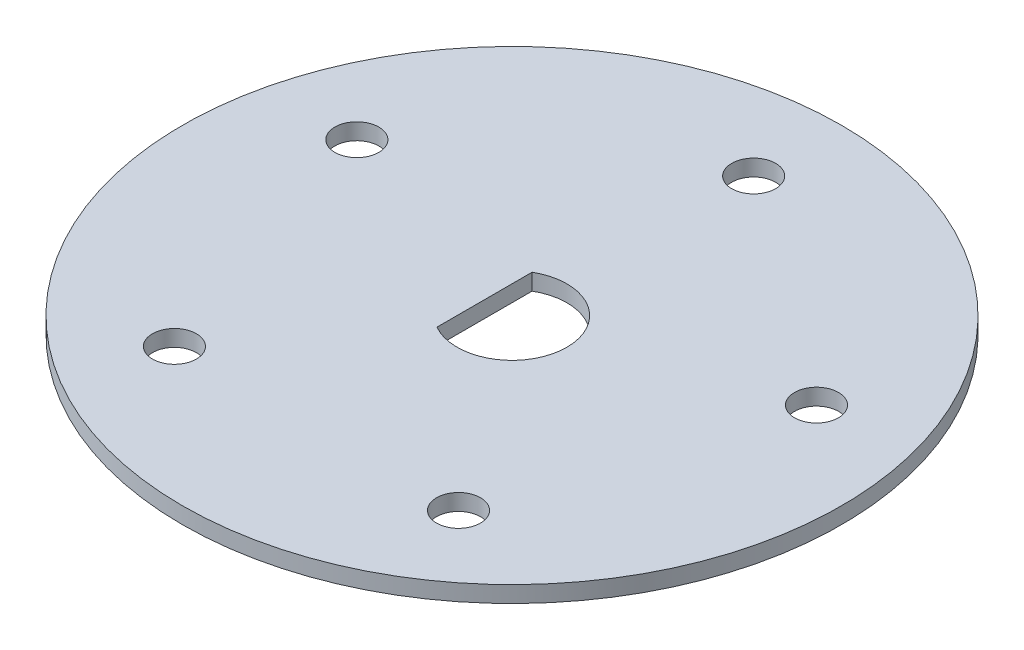
SolidWorks part; units mm, degrees
ref_plane "Front Plane" through (0, 0, 0) normal (0, 0, 1) x (1, 0, 0)
ref_plane "Top Plane" through (0, 0, 0) normal (0, 1, 0) x (1, 0, 0)
ref_plane "Right Plane" through (0, 0, 0) normal (1, 0, 0) x (0, 0, -1)
sketch "Sketch1" plane through (0, 0, 0) normal (0, 1, 0) x (1, 0, 0)
  line L2 (-3.175, 5.4993) -> (-3.175, -5.4993)
  circle A0 centre (0, 0) radius 38.1
  circle A2 centre (0, 27.94) radius 2.54
  circle A9 centre (26.5725, 8.6339) radius 2.54
  circle A10 centre (16.4227, -22.6039) radius 2.54
  circle A11 centre (-16.4227, -22.6039) radius 2.54
  circle A12 centre (-26.5725, 8.6339) radius 2.54
  arc A13 (-3.175, -5.4993) -> (-3.175, 5.4993) centre (0, 0) ccw
  point P10 (0, 0)
  point P18 (0, 0)
  point P19 (0, 0)
  dimension "D1" = 76.2
  dimension "D2" = 12.7
  dimension "D3" = 5.08
  dimension "D6" = 3.175
  dimension "D4" = 27.94
  dimension "D5" = 5
extrude "Boss-Extrude1" add sketch "Sketch1" along normal blind 1.8974 contours A0 | A12 | A11 | A10 | A9 | A13 L2 | A2
